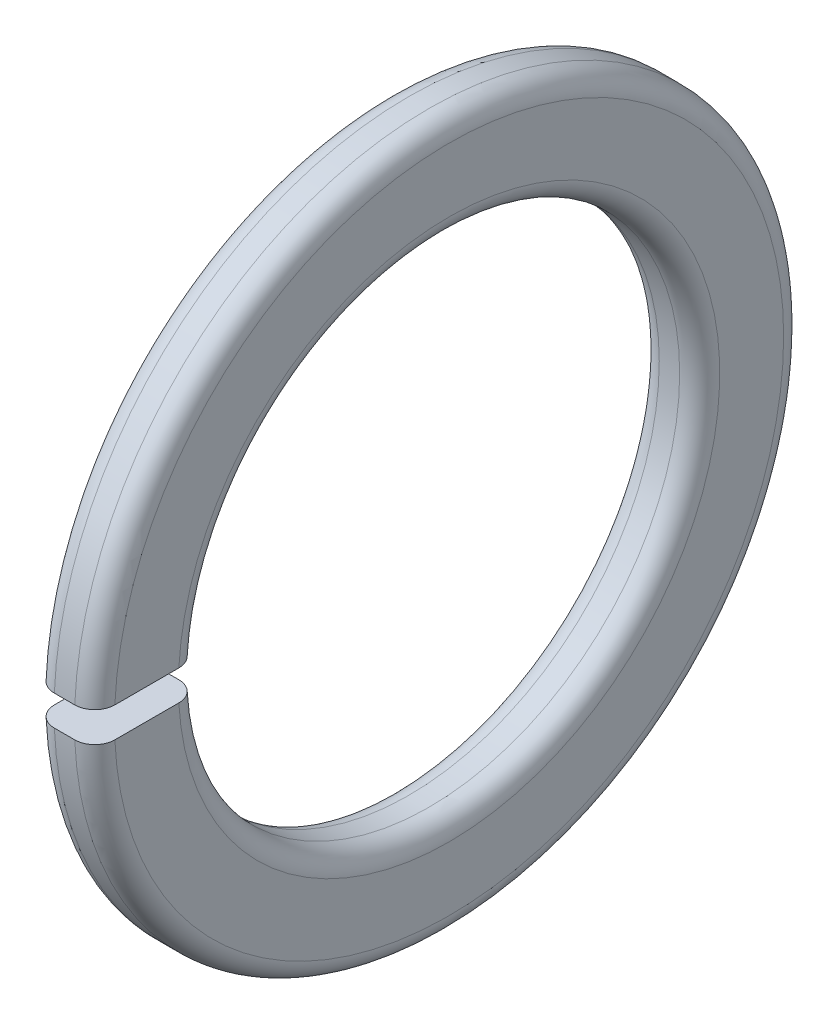
SolidWorks part; units mm, degrees
ref_plane "Plane1" through (0, 0, 0) normal (0, 0, 1) x (1, 0, 0)
ref_plane "Plane2" through (0, 0, 0) normal (0, 1, 0) x (1, 0, 0)
ref_plane "Plane3" through (0, 0, 0) normal (1, 0, 0) x (0, 0, -1)
sketch "Sketch1" plane through (0, 0, 0) normal (0, 0, 1) x (1, 0, 0)
  line L0 (-34.925, 0) -> (9.525, 0) construction
  line L1 (0, 35.8) -> (0, 44.25)
  line L2 (-2.65, 46.9) -> (-5.35, 46.9)
  line L3 (-8, 44.25) -> (-8, 35.8)
  line L4 (-5.35, 33.15) -> (-2.65, 33.15)
  arc A0 (-5.35, 33.15) -> (-8, 35.8) centre (-5.35, 35.8) cw
  arc A1 (0, 35.8) -> (-2.65, 33.15) centre (-2.65, 35.8) cw
  arc A2 (0, 44.25) -> (-2.65, 46.9) centre (-2.65, 44.25) ccw
  arc A3 (-5.35, 46.9) -> (-8, 44.25) centre (-5.35, 44.25) ccw
  point P8 (-8, 33.15)
  point P14 (0, 46.9)
  point P17 (-8, 46.9)
  dimension "Thickness" = 8
revolve "Base-Revolve" add sketch "Sketch1" angle 360 about L0
sketch "Sketch2" plane through (0, 0, 0) normal (-1, 0, 0) x (0, -1, 0)
  line L0 (-2, 0) -> (2, 0)
  line L1 (0, 0) -> (0, 12.7) construction
  line L2 (2, 0) -> (2, 47.838)
  line L3 (2, 47.838) -> (-2, 47.838)
  line L4 (-2, 47.838) -> (-2, 0)
  dimension "D1" = 4
  dimension "D2" = 47.838
extrude "Gap" cut sketch "Sketch2" along normal through all
equation "\"D1@Sketch2\" = \"Thickness@Sketch1\" * 0.5"
equation "\"D2@Sketch2\" = \"Outside_dia@Sketch1\" * 0.51"
